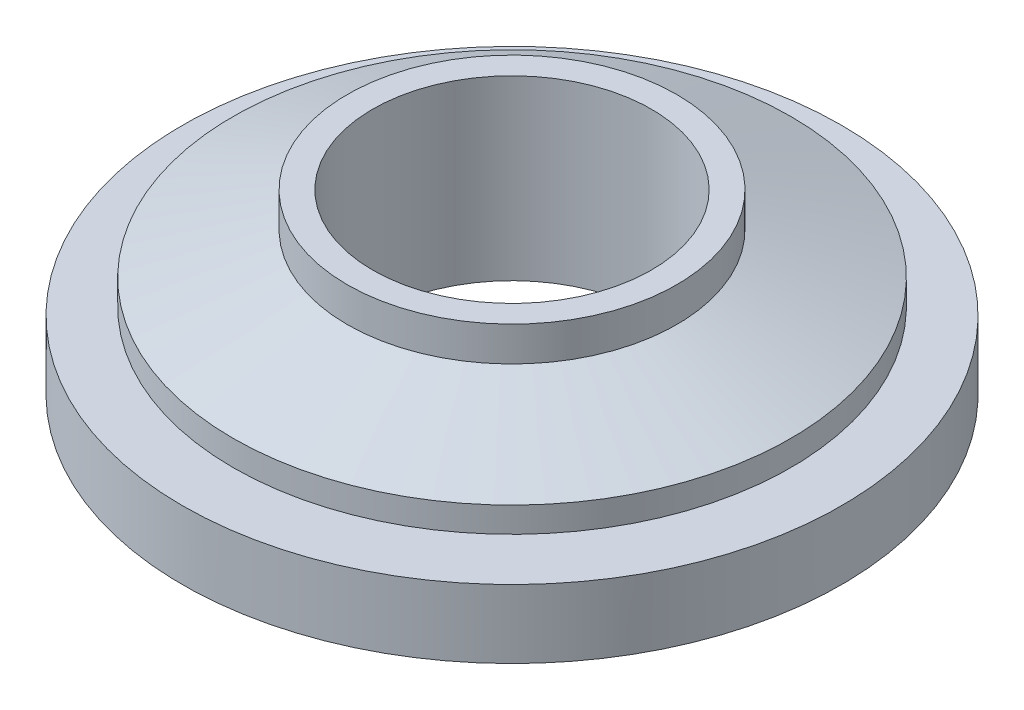
SolidWorks part; units mm, degrees
ref_plane "Спереди" through (0, 0, 0) normal (0, 0, 1) x (1, 0, 0)
ref_plane "Сверху" through (0, 0, 0) normal (0, 1, 0) x (1, 0, 0)
ref_plane "Справа" through (0, 0, 0) normal (1, 0, 0) x (0, 0, -1)
sketch "Sketch1" plane through (0, 0, 0) normal (0, 1, 0) x (1, 0, 0)
  circle A0 centre (0, 0) radius 7
  circle A1 centre (0, 0) radius 5.5
  dimension "D1" = 14
  dimension "D2" = 11
extrude "Boss-Extrude1" add sketch "Sketch1" along normal blind 3
chamfer "Chamfer1" distance 0.4 angle 70 1 edges at (0, 0, 7) first distance on face at (0, 0, 7)
sketch "Sketch2" plane through (0, 3, 0) normal (0, 1, 0) x (1, 0, 0)
  circle A0 centre (0, 0) radius 11
  circle A1 centre (0, 0) radius 5.5
  circle A2 centre (0, 0) radius 5.5 construction
  dimension "D1" = 22
extrude "Boss-Extrude2" add sketch "Sketch2" along normal blind 4
sketch "Sketch3" plane through (0, 7, 0) normal (0, 1, 0) x (1, 0, 0)
  circle A0 centre (0, 0) radius 6.5
  circle A1 centre (0, 0) radius 5.5 construction
  dimension "D1" = 1
extrude "Cut-Extrude1" cut sketch "Sketch3" against normal blind 1 flip side to cut
chamfer "Chamfer2" distance 2 angle 70 1 edges at (0, 6, 11) first distance on face at (0, 3, 11)
sketch "Sketch5" plane through (0, 0, 0) normal (0, -1, 0) x (1, 0, 0)
  circle A0 centre (0, 0) radius 8.6
  circle A1 centre (0, 0) radius 13
  circle A2 centre (0, 0) radius 6.6 construction
  circle A3 centre (0, 0) radius 11 construction
  dimension "D1" = 2
  dimension "D2" = 2
extrude "Boss-Extrude3" add sketch "Sketch5" against normal offset from surface (2.7 mm away) 0.3 separate body up to face at (0, 3, 11)
